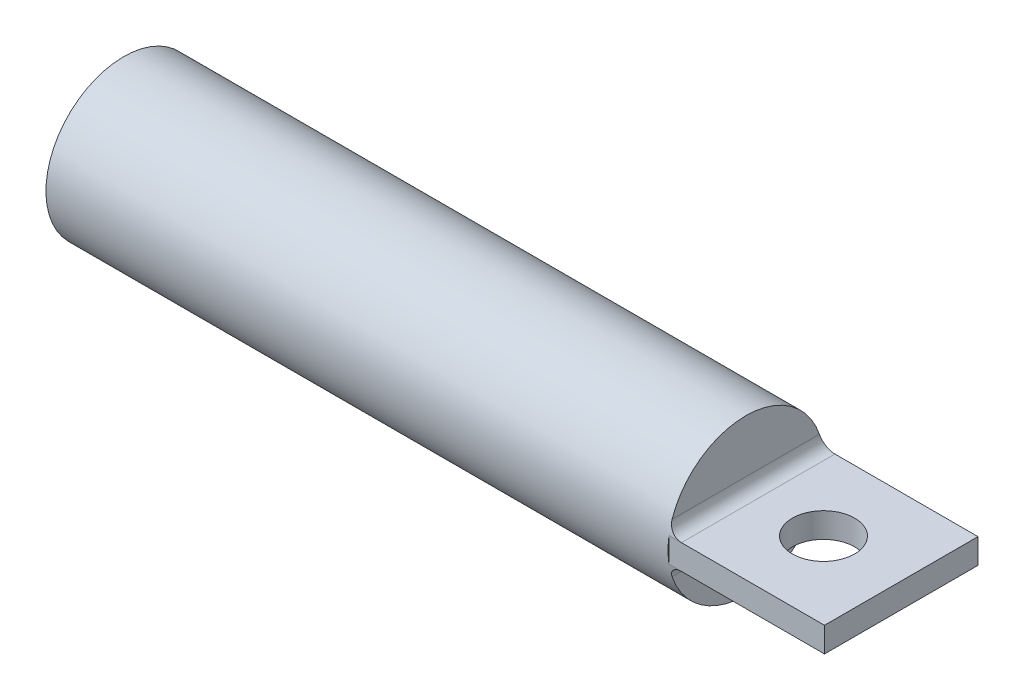
SolidWorks part; units mm, degrees
ref_plane "Front Plane" through (0, 0, 0) normal (0, 0, 1) x (1, 0, 0)
ref_plane "Top Plane" through (0, 0, 0) normal (0, 1, 0) x (1, 0, 0)
ref_plane "Right Plane" through (0, 0, 0) normal (1, 0, 0) x (0, 0, -1)
sketch "Sketch1" plane through (0, 0, 0) normal (1, 0, 0) x (0, 0, -1)
  circle A0 centre (0, 0) radius 3.175
  dimension "D1" = 6.35
extrude "Boss-Extrude1" add sketch "Sketch1" along normal blind 25.4
sketch "Sketch2" plane through (25.4, 0, 0) normal (1, 0, 0) x (0, 0, -1)
  line L0 (-3.1341, 0.508) -> (3.1341, 0.508)
  line L1 (3.1341, 0.508) -> (3.1341, -0.508)
  line L2 (3.1341, -0.508) -> (-3.1341, -0.508)
  line L3 (-3.1341, -0.508) -> (-3.1341, 0.508)
  circle A0 centre (0, 0) radius 3.175 construction
  point P5 (3.1341, 0)
  dimension "D1" = 1.016
extrude "Boss-Extrude2" add sketch "Sketch2" along normal blind 6.35
sketch "Sketch3" plane through (0, 0.508, 0) normal (0, 1, 0) x (1, 0, 0)
  line L0 (31.75, 0) -> (25.4, 0) construction
  line L1 (31.75, 3.1341) -> (31.75, -3.1341) construction
  line L2 (25.4, 3.1341) -> (25.4, -3.1341) construction
  line L3 (28.575, -3.1341) -> (28.575, 3.1341) construction
  line L4 (31.75, -3.1341) -> (25.4, -3.1341) construction
  line L5 (31.75, 3.1341) -> (25.4, 3.1341) construction
  circle A0 centre (28.575, 0) radius 1.27
  dimension "D1" = 2.54
extrude "Cut-Extrude1" cut sketch "Sketch3" against normal through all
fillet "Fillet1" radius 0.508 2 edges at (25.4, 0.508, 0) (25.4, -0.508, 0)
